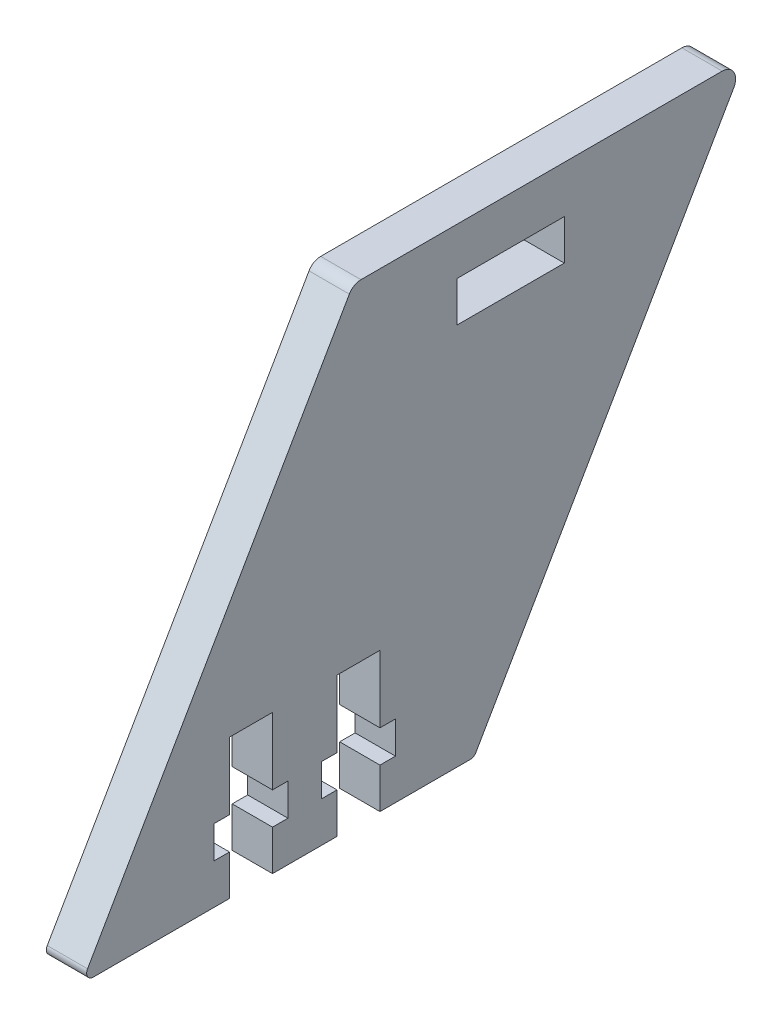
SolidWorks part; units mm, degrees
material "Beech"
ref_plane "Front Plane" through (0, 0, 0) normal (0, 0, 1) x (1, 0, 0)
ref_plane "Top Plane" through (0, 0, 0) normal (0, 1, 0) x (1, 0, 0)
ref_plane "Right Plane" through (0, 0, 0) normal (1, 0, 0) x (0, 0, -1)
sketch "Sketch1" plane through (0, 0, 0) normal (1, 0, 0) x (0, 0, -1)
  line L0 (-4, 0) -> (4, 0) construction
  line L1 (-5.6, 0) -> (-5.6, 3)
  line L2 (-5.6, 3) -> (-6.75, 3)
  line L3 (-6.75, 3) -> (-6.75, 5.4)
  line L4 (-6.75, 5.4) -> (-1.25, 5.4) construction
  line L5 (-1.25, 5.4) -> (-1.25, 3)
  line L6 (-1.25, 3) -> (-2.4, 3)
  line L7 (-2.4, 3) -> (-2.4, 0)
  line L8 (-2.4, 0) -> (2.4, 0)
  line L9 (2.4, 0) -> (2.4, 3)
  line L10 (2.4, 3) -> (1.25, 3)
  line L11 (1.25, 3) -> (1.25, 5.4)
  line L12 (1.25, 5.4) -> (6.75, 5.4) construction
  line L13 (6.75, 5.4) -> (6.75, 3)
  line L14 (6.75, 3) -> (5.6, 3)
  line L15 (5.6, 3) -> (5.6, 0)
  line L16 (5.6, 0) -> (12.6, 0)
  line L17 (12.6, 0) -> (32.8073, 35)
  line L18 (-6.75, 5.4) -> (-5.6, 5.4)
  line L19 (-5.6, 5.4) -> (-5.6, 10.4)
  line L20 (-5.6, 10.4) -> (-2.4, 10.4)
  line L21 (-2.4, 10.4) -> (-2.4, 5.4)
  line L22 (-2.4, 5.4) -> (-1.25, 5.4)
  line L23 (1.25, 5.4) -> (2.4, 5.4)
  line L24 (2.4, 5.4) -> (2.4, 10.4)
  line L25 (2.4, 10.4) -> (5.6, 10.4)
  line L26 (5.6, 10.4) -> (5.6, 5.4)
  line L27 (5.6, 5.4) -> (6.75, 5.4)
  line L28 (32.8073, 35) -> (3.6073, 35)
  line L29 (3.6073, 35) -> (-16.6, 0)
  line L30 (-16.6, 0) -> (-5.6, 0)
  line L31 (18.2073, 35) -> (15.3205, 30) construction
  line L33 (11.3205, 28.5) -> (19.3205, 28.5)
  line L34 (11.3205, 28.5) -> (11.3205, 31.5)
  line L35 (11.3205, 31.5) -> (19.3205, 31.5)
  line L36 (19.3205, 28.5) -> (19.3205, 31.5)
  line L37 (11.3205, 28.5) -> (19.3205, 31.5) construction
  line L38 (11.3205, 31.5) -> (19.3205, 28.5) construction
  point P3 (0, 0)
  point P10 (-4, 5.4)
  point P23 (4, 5.4)
  dimension "D1" = 8
  dimension "D2" = 5.5
  dimension "D3" = 3.2
  dimension "D4" = 3.2
  dimension "D5" = 2.4
  dimension "D6" = 3
  dimension "D7" = 5
  dimension "D8" = 7
  dimension "D9" = 11
  dimension "D10" = 120
  dimension "D11" = 35
  dimension "D12" = 5
  dimension "D13" = 8
  dimension "D14" = 3
extrude "Boss-Extrude1" add sketch "Sketch1" along normal blind 3
fillet "Fillet1" radius 1 2 edges at (1.5, 35, -32.8073) (1.5, 35, -3.6073)
fillet "Fillet2" radius 0.5 2 edges at (1.5, 0, 16.6) (1.5, 0, -12.6)
